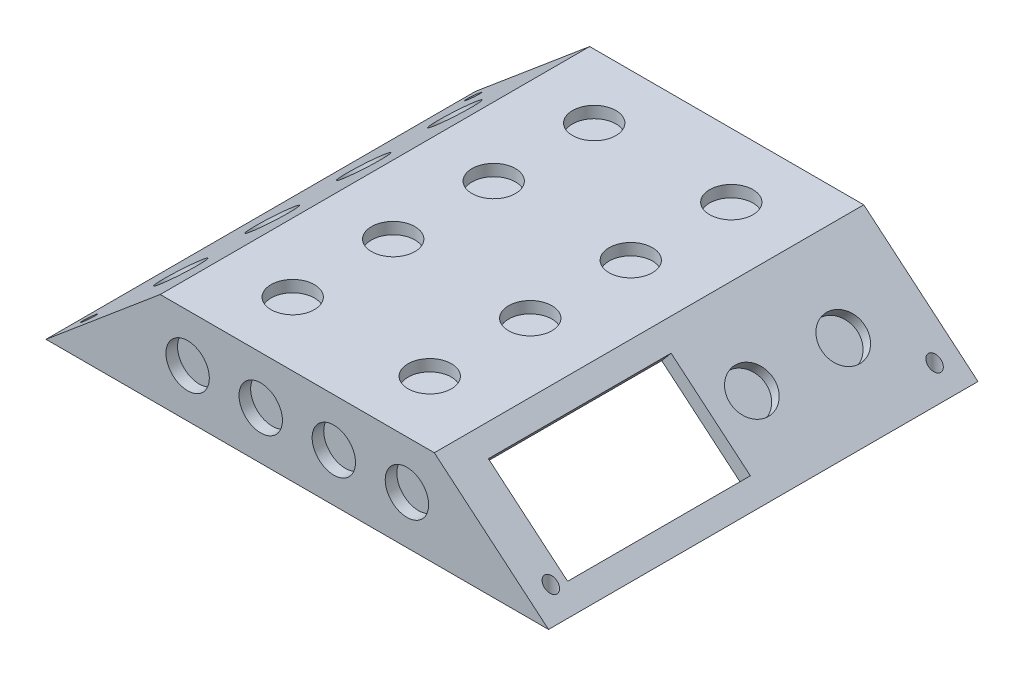
SolidWorks part; units mm, degrees
ref_plane "Alzado" through (0, 0, 0) normal (0, 0, 1) x (1, 0, 0)
ref_plane "Planta" through (0, 0, 0) normal (0, 1, 0) x (1, 0, 0)
ref_plane "Vista lateral" through (0, 0, 0) normal (1, 0, 0) x (0, 0, -1)
sketch "Croquis2" plane through (0, 0, 0) normal (0, 0, 1) x (1, 0, 0)
  line L0 (-55, 0) -> (-30, 0)
  line L1 (-30, 0) -> (-30, 21)
  line L2 (-30, 21) -> (-55, 0)
  line L3 (30, 21) -> (55, 0)
  line L4 (-30, 21) -> (30, 21)
  line L5 (-30, 21) -> (-30, 0)
  line L6 (-30, 0) -> (30, 0)
  line L7 (30, 21) -> (30, 0)
  line L8 (55, 0) -> (30, 0)
  dimension "D1" = 110
  dimension "D2" = 60
  dimension "D3" = 21
extrude "Saliente-Extruir1" add sketch "Croquis2" along normal blind 94 contours L7 L4 L1 L6 | L1 L2 L0 | L8 L3 L7 region at (-38.3333, 7, 0) region at (0, 10.5, 0) region at (38.3333, 7, 0)
sketch "Croquis3" plane through (0, 0, 0) normal (0, 0, -1) x (-1, 0, 0)
  line L0 (-50.0248, 0) -> (-28.8343, 17.8)
  line L1 (55, 0) -> (-55, 0) construction
  line L2 (-28.8343, 17.8) -> (28.8343, 17.8)
  line L3 (28.8343, 17.8) -> (50.0248, 0)
  line L4 (50.0248, 0) -> (-50.0248, 0)
  line L5 (-30, 21) -> (-55, 0) construction
  line L6 (30, 21) -> (-30, 21) construction
  line L9 (30, 21) -> (55, 0) construction
  line L11 (55, 0) -> (50.0248, 0)
  line M1 (-55, 0) -> (55, 0)
  dimension "D1" = 3.2
  dimension "D2" = 3.2
  dimension "D3" = 3.2
extrude "Cortar-Extruir1" cut sketch "Croquis3" against normal blind 91 contours L3 L2 L0 M1 region at (0, 8.1028, 0)
sketch "Croquis7" plane through (0, 21, 0) normal (0, 1, 0) x (1, 0, 0)
  line L0 (-55, -94) -> (-55, 0) construction
  line L1 (-55, 0) -> (55, 0) construction
  line L2 (55, 0) -> (55, -94) construction
  line L3 (55, -94) -> (-55, -94) construction
  line L4 (-50.5, 0) -> (-50.5, -94) construction
  line L5 (-55, -5) -> (55, -5) construction
  line L6 (50.5, 0) -> (50.5, -94) construction
  line L7 (-55, -89) -> (55, -89) construction
  line L8 (0, 0) -> (0, -94) construction
  dimension "D1" = 5
  dimension "D2" = 50.5
  dimension "D3" = 50.5
  dimension "D4" = 5
hole_wizard "Taladro de margen para M2.51" positions "Croquis11" profile "Croquis10" hole size "M2.5" standard "ISO" end condition through all
sketch "Croquis11" plane through (0, 21, 0) normal (0, 1, 0) x (1, 0, 0)
  line L0 (-50.5, 0) -> (-50.5, -94) construction
  line L1 (-55, -5) -> (55, -5) construction
  line L2 (50.5, 0) -> (50.5, -94) construction
  line L3 (-55, -89) -> (55, -89) construction
  point P0 (-50.5, -5)
  point P6 (50.5, -5)
  point P10 (-50.5, -89)
  point P14 (50.5, -89)
sketch "Croquis10" plane through (-50.5, 21, 5) normal (1, 0, 0) x (0, 0, 1)
  line L0 (0, 0) -> (0, 21)
  line L1 (0, 21) -> (1.35, 21)
  line L2 (1.35, 21) -> (1.35, 0)
  line L5 (1.35, 0) -> (0, 0)
  line L11 (0, -6.35) -> (0, 107.95) construction
  dimension "Diámetro de taladro hasta el siguiente" = 2.7
  dimension "Profundidad de taladro hasta el siguiente" = 21
sketch "Croquis12" plane through (22.7533, 27.0872, 0) normal (0.6432, 0.7657, 0) x (0, 0, -1)
  line L0 (-94, -9.4641) -> (0, -9.4641) construction
  line L1 (-86, -14.4641) -> (-46, -14.4641)
  line L2 (-86, -14.4641) -> (-86, -37.1138)
  line L3 (-86, -37.1138) -> (-46, -37.1138)
  line L4 (-46, -14.4641) -> (-46, -37.1138)
  line L5 (-94, -42.1138) -> (0, -42.1138) construction
  line L6 (-94, -9.4641) -> (-94, -42.1138) construction
  dimension "D1" = 5
  dimension "D2" = 5
  dimension "D3" = 8
  dimension "D4" = 40
extrude "Cortar-Extruir2" cut sketch "Croquis12" against normal up to next
sketch "Croquis13" plane through (0, 21, 0) normal (0, 1, 0) x (1, 0, 0)
  line L0 (0, 0) -> (0, -94) construction
  line L1 (-30, 0) -> (30, 0) construction
  line L2 (-30, -94) -> (30, -94) construction
  circle A0 centre (-15, -14) radius 4.75
  circle A1 centre (-15, -36) radius 4.75
  circle A2 centre (-15, -58) radius 4.75
  circle A3 centre (-15, -80) radius 4.75
  circle A4 centre (15, -14) radius 4.75
  circle A5 centre (15, -36) radius 4.75
  circle A6 centre (15, -58) radius 4.75
  circle A7 centre (15, -80) radius 4.75
  dimension "D1" = 9.5
  dimension "D2" = 14
  dimension "D3" = 22
  dimension "D4" = 14
  dimension "D5" = 22
  dimension "D6" = 22
  dimension "D7" = 15
extrude "Cortar-Extruir3" cut sketch "Croquis13" against normal blind 2.54
sketch "Croquis14" plane through (-22.7533, 27.0872, 0) normal (-0.6432, 0.7657, 0) x (0, 0, 1)
  line L0 (0, -25.7889) -> (94, -25.7889) construction
  line L1 (0, -9.4641) -> (0, -42.1138) construction
  line L2 (94, -9.4641) -> (94, -42.1138) construction
  circle A0 centre (17, -25.7889) radius 4.75
  circle A1 centre (37, -25.7889) radius 4.75
  circle A2 centre (57, -25.7889) radius 4.75
  circle A3 centre (77, -25.7889) radius 4.75
  dimension "D1" = 9.5
  dimension "D2" = 17
  dimension "D3" = 20
  dimension "D4" = 17
  dimension "D5" = 20
  dimension "D6" = 20
extrude "Cortar-Extruir4" cut sketch "Croquis14" against normal blind 2.54
sketch "Croquis15" plane through (22.7533, 27.0872, 0) normal (0.6432, 0.7657, 0) x (0, 0, -1)
  line L0 (0, -25.7889) -> (-94, -25.7889) construction
  line L1 (0, -9.4641) -> (0, -42.1138) construction
  line L2 (-94, -9.4641) -> (-94, -42.1138) construction
  circle A0 centre (-17, -25.7889) radius 4.75
  circle A1 centre (-37, -25.7889) radius 4.75
  dimension "D1" = 9.5
  dimension "D2" = 17
  dimension "D3" = 20
extrude "Cortar-Extruir5" cut sketch "Croquis15" against normal blind 2.54
sketch "Croquis17" plane through (0, 0, 94) normal (0, 0, 1) x (1, 0, 0)
  line L0 (0, 21) -> (0, 0) construction
  line L1 (-30, 21) -> (30, 21) construction
  line L2 (-55, 0) -> (55, 0) construction
  line L3 (-42.5, 10.5) -> (42.5, 10.5) construction
  line L4 (-30, 21) -> (-55, 0) construction
  line L5 (30, 21) -> (55, 0) construction
  circle A0 centre (-8, 10.5) radius 4.75
  circle A1 centre (8, 10.5) radius 4.75
  circle A2 centre (-24, 10.5) radius 4.75
  circle A3 centre (24, 10.5) radius 4.75
  dimension "D1" = 9.5
  dimension "D2" = 8
  dimension "D3" = 16
extrude "Cortar-Extruir7" cut sketch "Croquis17" against normal blind 2.54
